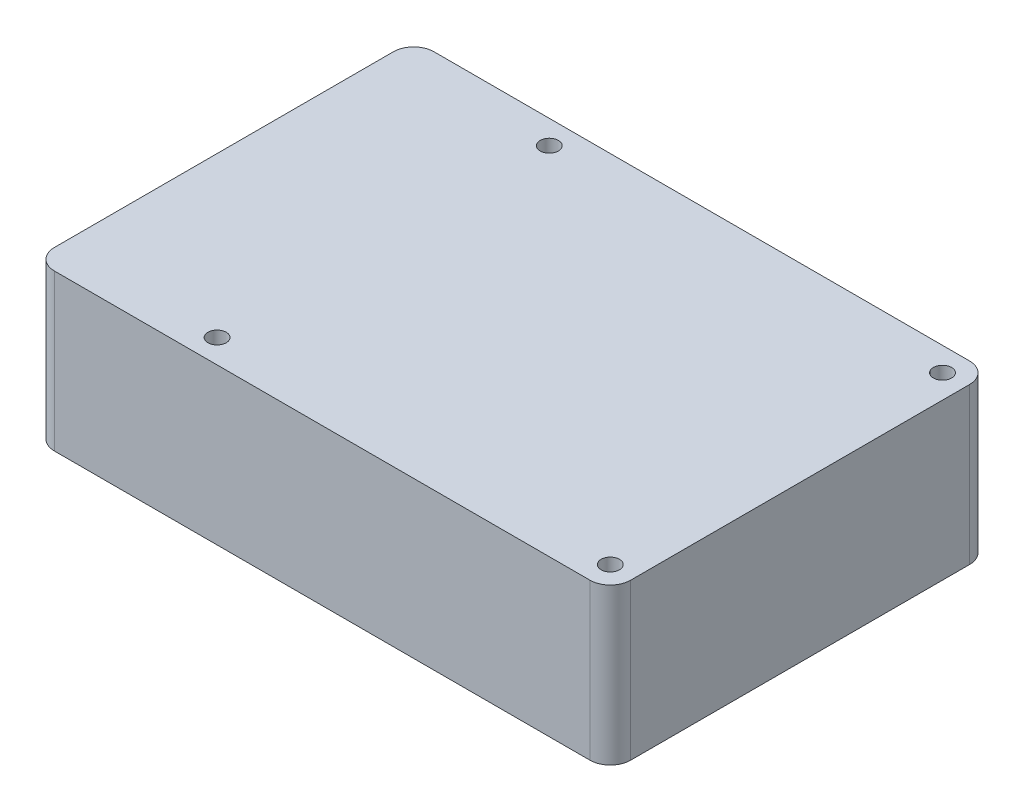
SolidWorks part; units mm, degrees
ref_plane "Alzado" through (0, 0, 0) normal (0, 0, 1) x (1, 0, 0)
ref_plane "Planta" through (0, 0, 0) normal (0, 1, 0) x (1, 0, 0)
ref_plane "Vista lateral" through (0, 0, 0) normal (1, 0, 0) x (0, 0, -1)
sketch "Croquis1" plane through (0, 0, 0) normal (0, 1, 0) x (1, 0, 0)
  line L1 (42.5, -28) -> (-42.5, -28)
  line L2 (42.5, -28) -> (42.5, 28)
  line L3 (42.5, 28) -> (-42.5, 28)
  line L4 (-42.5, -28) -> (-42.5, 28)
  line L5 (42.5, -28) -> (-42.5, 28) construction
  line L6 (42.5, 28) -> (-42.5, -28) construction
  point P0 (0, 0)
  dimension "D1" = 85
  dimension "D2" = 56
extrude "Saliente-Extruir1" add sketch "Croquis1" along normal blind 23
fillet "Redondeo1" radius 3 4 edges at (-42.5, 11.5, -28) (42.5, 11.5, -28) (-42.5, 11.5, 28) (42.5, 11.5, 28)
sketch "Croquis2" plane through (0, 23, 0) normal (0, 1, 0) x (1, 0, 0)
  line L0 (42.5, -25) -> (42.5, 25) construction
  line L5 (-19, 24.5) -> (39, 24.5) construction
  line L6 (-19, 24.5) -> (-19, -24.5) construction
  line L7 (-19, -24.5) -> (39, -24.5) construction
  line L8 (39, 24.5) -> (39, -24.5) construction
  circle A0 centre (-19, 24.5) radius 1.35
  circle A4 centre (39, 24.5) radius 1.35
  circle A5 centre (39, -24.5) radius 1.35
  circle A6 centre (-19, -24.5) radius 1.35
  point P8 (-19, 0)
  dimension "D4" = 2.7
  dimension "D1" = 3.5
  dimension "D2" = 49
  dimension "D3" = 58
extrude "Cortar-Extruir1" cut sketch "Croquis2" against normal through all
sketch "Croquis3" plane through (0, 0, 0) normal (0, -1, 0) x (1, 0, 0)
  line L0 (-39.5, 28) -> (39.5, 28) construction
  line L1 (39.5, -28) -> (-39.5, -28) construction
  line L13 (-44.25, -35.15) -> (44.25, -35.15)
  line L15 (44.25, 35.15) -> (-44.25, 35.15)
  line L18 (49.25, 25) -> (49.25, -25)
  line L19 (49.25, 30.15) -> (49.25, -30.15)
  line L21 (-49.25, -25) -> (-49.25, 25)
  line L22 (-49.25, -30.15) -> (-49.25, 30.15)
  arc A0 (49.25, 30.15) -> (44.25, 35.15) centre (44.25, 30.15) ccw
  arc A1 (44.25, -35.15) -> (49.25, -30.15) centre (44.25, -30.15) ccw
  arc A2 (-49.25, -30.15) -> (-44.25, -35.15) centre (-44.25, -30.15) ccw
  arc A3 (-49.25, 30.15) -> (-44.25, 35.15) centre (-44.25, 30.15) cw
  point P4 (-49.25, 35.15)
  point P6 (-48.351, 35.15)
  point P7 (-49.25, -35.15)
  point P8 (49.25, -35.15)
  point P10 (-49.25, -34.2707)
  point P12 (49.25, -34.2707)
  point P15 (49.25, 35.15)
  point P16 (49.25, 34.2707)
  dimension "D5" = 5
  dimension "D1" = 7.15
  dimension "D2" = 7.15
  dimension "D3" = 6.75
  dimension "D4" = 6.75
extrude "Saliente-Extruir2" [suppressed] add sketch "Croquis3" against normal blind 33
sketch "Croquis4" plane through (0, 0, 0) normal (0, -1, 0) x (1, 0, 0)
  circle A1 centre (-19, 24.5) radius 1.35
  circle A2 centre (-19, 24.5) radius 1.35
  circle A3 centre (39, 24.5) radius 1.35
  circle A4 centre (39, 24.5) radius 1.35
  circle A5 centre (39, -24.5) radius 1.35
  circle A6 centre (39, -24.5) radius 1.35
  circle A7 centre (-19, -24.5) radius 1.35
  circle A8 centre (-19, -24.5) radius 1.35
  dimension "D1" = 0
  dimension "D2" = 0
  dimension "D3" = 0
  dimension "D4" = 0
extrude "Cortar-Extruir2" [suppressed] cut sketch "Croquis4" against normal through all
